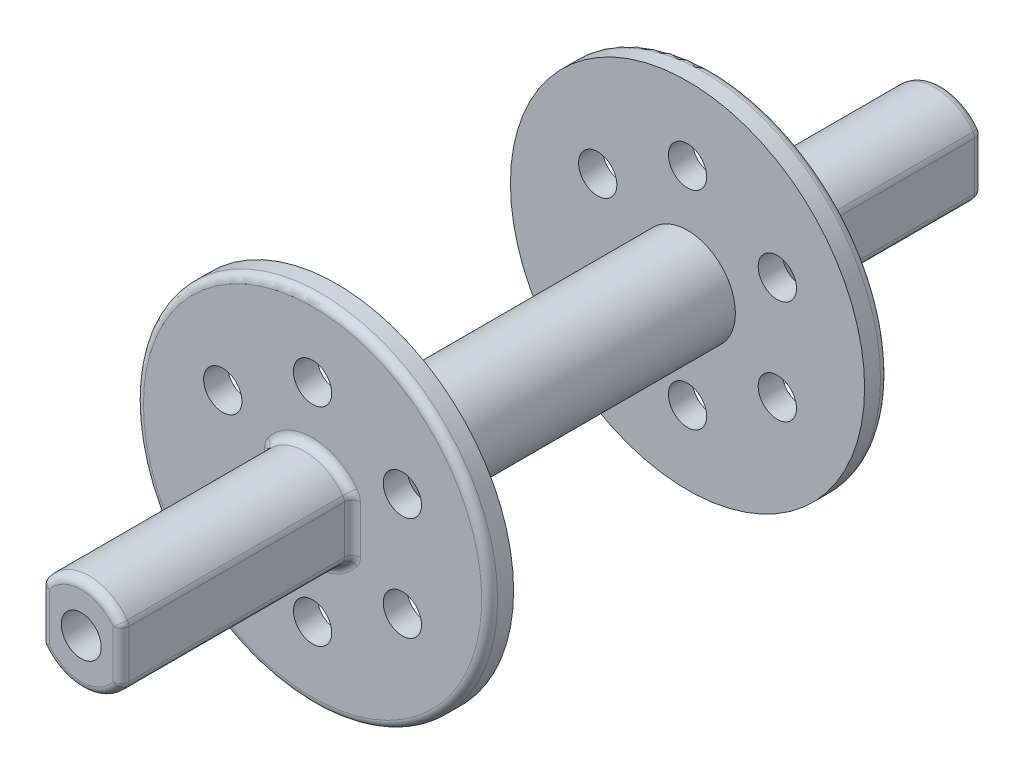
SolidWorks part; units mm, degrees
ref_plane "Alzado" through (0, 0, 0) normal (0, 0, 1) x (1, 0, 0)
ref_plane "Planta" through (0, 0, 0) normal (0, 1, 0) x (1, 0, 0)
ref_plane "Vista lateral" through (0, 0, 0) normal (1, 0, 0) x (0, 0, -1)
sketch "Croquis1" plane through (0, 0, 0) normal (1, 0, 0) x (0, 0, -1)
  line L0 (-55.0748, 0) -> (55.0748, 0) construction
  line L5 (-25, 22.2) -> (-25, 6)
  line L7 (-54, 6) -> (-54, 2.5)
  line L8 (-54, 2.5) -> (-25, 2.5)
  line L9 (0, 0) -> (0, 23.4689) construction
  line L12 (-25, 2.5) -> (0, 2.5)
  line L14 (-25, 22.2) -> (-22, 22.2)
  line L16 (-25, 6) -> (-26, 6)
  line L17 (-26, 6) -> (-54, 6)
  line L19 (-22, 22.2) -> (-22, 6)
  line L20 (-22, 6) -> (0, 6)
  line L21 (0, 6) -> (0, 2.5)
  dimension "D1" = 1
  dimension "D2" = 108
  dimension "D3" = 5
  dimension "D4" = 44.4
  dimension "D5" = 12
  dimension "D6" = 50
  dimension "D7" = 3
revolve "Revolución4" add sketch "Croquis1" angle 360 about L0
sketch "Croquis2" plane through (0, 0, 0) normal (1, 0, 0) x (0, 0, -1)
  line L0 (-26, -6) -> (-26, 6)
  line L2 (-54, -6) -> (-25, -6) construction
  point P3 (-26, 0)
split line "Línea de partición1"
sketch "Croquis3" plane through (0, 0, 54) normal (0, 0, 1) x (1, 0, 0)
  line L1 (-5, 3.3166) -> (5, 3.3166) construction
  line L2 (-5, 3.3166) -> (-5, -3.3166)
  line L3 (-5, -3.3166) -> (5, -3.3166) construction
  line L4 (5, 3.3166) -> (5, -3.3166)
  line L5 (-5, 3.3166) -> (5, -3.3166) construction
  line L6 (-5, -3.3166) -> (5, 3.3166) construction
  circle A0 centre (0, 0) radius 6 construction
  circle A1 centre (0, 0) radius 6 construction
  arc A2 (-5, 3.3166) -> (-5, -3.3166) centre (0, 0) ccw
  arc A3 (5, -3.3166) -> (5, 3.3166) centre (0, 0) ccw
  point P0 (0, 0)
  dimension "D1" = 10
extrude "Cortar-Extruir1" cut sketch "Croquis3" against normal up to surface (29 mm away) up to face at (6, 0, 25)
fillet "Redondeo2" radius 1 12 edges at (-5, 0, 25) (0, 6, 25) (0, -6, 25) (5, 0, 54) (-5, 0, 54) (5, 0, 25) (22.2, 0, 25) (0, -6, 54) (0, 6, 54) (-5, 3.3166, 40) (5, 3.3166, 40) (5, -3.3166, 40)
mirror "Simetría1" about plane through (0, 0, 0) normal (0, 0, 1) of bodies 106
sketch "Croquis4" plane through (0, 0, 0) normal (0, 0, 1) x (1, 0, 0)
  circle A0 centre (0, 13) radius 2.4
  dimension "D1" = 4.8
  dimension "D2" = 13
extrude "Cortar-Extruir2" cut sketch "Croquis4" against normal through all both and the other way through all
pattern_circular "MatrizC1" count 6 over 360 about axis through (0, 0, 0) along (0, 0, 1) of "Cortar-Extruir2"
